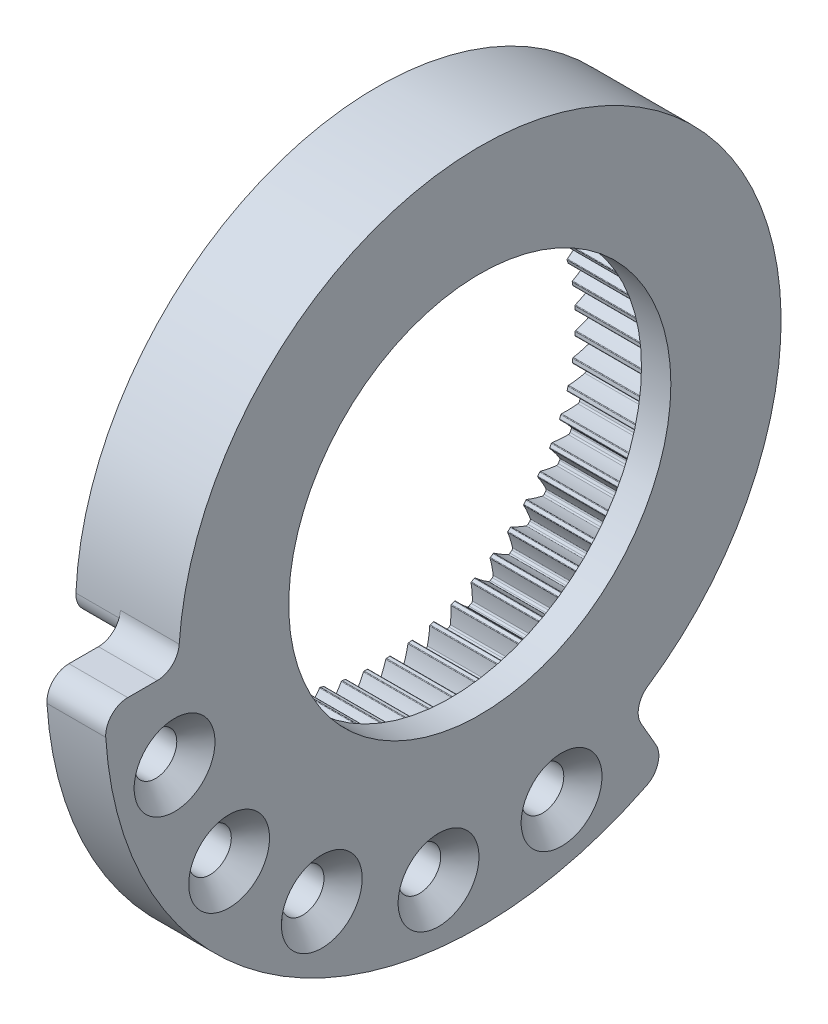
SolidWorks part; units mm, degrees
ref_plane "Plane1" through (0, 0, 0) normal (0, 0, 1) x (1, 0, 0)
ref_plane "Plane2" through (0, 0, 0) normal (0, 1, 0) x (1, 0, 0)
ref_plane "Plane3" through (0, 0, 0) normal (1, 0, 0) x (0, 0, -1)
other "Configuration Table"
sketch "HoldingSke" plane through (0, 0, 0) normal (0, 1, 0) x (1, 0, 0)
  line L0 (0, 0) -> (1.1184, -1.6581)
  line L1 (-15, 0) -> (100, 0) construction
  line L2 (0, 0) -> (-2.1039, 2.3779)
  line L3 (0, 0) -> (-11.863, 4.5341)
  line L4 (0, 0) -> (4.8292, 7.1596)
  line L5 (0, 0) -> (-23.7986, -8.8762)
  line L6 (0, 0) -> (-10.5278, -7.1032)
  line L7 (-2.1039, 2.3779) -> (3.3635, 27.1825)
  line L8 (-76.2, 2.8779) -> (-54.61, 2.8779)
  line L9 (-71.009, 38.7566) -> (-53.1078, 45.2721)
  line L10 (-76.2, 71.12) -> (104.1128, 71.12)
  line L11 (0, 0) -> (-7, 0)
  line L12 (-76.2, 101.6) -> (-76.181, 101.6)
  line L13 (24.9733, 27.94) -> (52.9518, 28.4284)
  line L14 (24.9733, 27.94) -> (24.9743, 27.94)
  line L15 (24.9733, 27.94) -> (100.4006, 29.5858)
  circle A0 centre (0, 0) radius 21
  circle A1 centre (0, 0) radius 12.7
  circle A2 centre (0, 0) radius 12.7
  dimension "Num_teeth" = 56
  dimension "Pitch_radius" = 180.3128
  dimension "Width" = 7
  dimension "Diameter" = 42
sketch "BasProSke" plane through (0, 0, 0) normal (0, 1, 0) x (1, 0, 0)
  line L0 (-10, 0) -> (60, 0) construction
  line L1 (0, 13.5) -> (0, 21)
  line L2 (0, 13.5) -> (7, 13.5)
  line L3 (7, 13.5) -> (7, 21)
  line L4 (7, 21) -> (0, 21)
  dimension "Thickness" = 7
  dimension "Diameter" = 42
revolve "Base-Revolve" add sketch "BasProSke" angle 360 about L0
sketch "TooCutSke" plane through (0, 0, 0) normal (1, 0, 0) x (0, 0, -1)
  line L3 (0.4401, 13.9931) -> (0.4401, 53.6633) construction
  line L4 (0, 0) -> (0, 59.563) construction
  line L5 (0, 0) -> (-3.8312, 68.22) construction
  line L6 (-6.1069, 11.5158) -> (37.1194, 13.9434) construction
  circle A0 centre (0, 0) radius 14 construction
  circle A1 centre (0, 0) radius 14.626 construction
  circle A2 centre (0, 0) radius 11.8401 construction
  circle A3 centre (0, 0) radius 13.4746 construction
  arc A4 (0.6176, 13.4604) -> (0.1647, 14.6251) centre (-6.1069, 11.5158) ccw
  arc A5 (0.6176, 13.4604) -> (-0.6176, 13.4604) centre (0, 0) ccw
  arc A6 (0.1647, 14.6251) -> (-0.1647, 14.6251) centre (0, 0) ccw
  arc A7 (-0.1647, 14.6251) -> (-0.6176, 13.4604) centre (6.1069, 11.5158) ccw
extrude "ToothCut" cut sketch "TooCutSke" along normal through all
fillet "Breaks" radius 0.05 2 edges at (3.5, 13.4862, 0.6101) (3.5, 13.4862, -0.6101)
fillet "RootFillets" radius 0.126 2 edges at (3.5, 14.6251, 0.1647) (3.5, 14.6251, -0.1647)
pattern_circular "TeethCuts" count 56 every 6.429 about axis through (-10, 0, 0) along (1, 0, 0) of "RootFillets", "Breaks", "ToothCut"
sketch "Sketch1" plane through (0, 0, 0) normal (-1, 0, 0) x (0, 0, 1)
  circle A0 centre (0, 0) radius 20.5
  circle A1 centre (0, 0) radius 21
  dimension "1" = 41
extrude "Cut-Extrude1" cut sketch "Sketch1" against normal through all
sketch "Sketch2" plane through (7, 0, 0) normal (1, 0, 0) x (0, 0, -1)
  circle A0 centre (0, 0) radius 20.5
  circle A1 centre (0, 0) radius 13
  dimension "7.5" = 26
extrude "Boss-Extrude1" add sketch "Sketch2" against normal blind 2
sketch "Sketch3" plane through (0, 0, 0) normal (-1, 0, 0) x (0, 0, 1)
  line L0 (0, 0) -> (28.6774, 0) construction
  line L1 (0, 0) -> (28.8819, -7.7389) construction
  line L2 (20.5, 0) -> (25.5, 0)
  line L3 (-10.2547, -17.7508) -> (-12.7547, -22.0809)
  arc A0 (-10.2547, -17.7508) -> (20.5, 0) centre (0, 0) ccw
  arc A1 (25.5, 0) -> (-12.7547, -22.0809) centre (0, 0) cw
  circle A2 centre (0, 0) radius 20.5 construction
  arc A3 (-10.2547, -17.7508) -> (20.5, 0) centre (0, 0) ccw
  dimension "D3" = 25.5
  dimension "D4" = 0
  dimension "D1" = 15
  dimension "D2" = 120
  dimension "D5" = 5
  dimension "D6" = 5
  dimension "D7" = 44.17
extrude "Boss-Extrude2" add sketch "Sketch3" against normal up to surface (7 mm away) contours A1 L2 A0 L3 up to face at (7, 0, 20.5)
sketch "Sketch4" plane through (0, 0, 0) normal (-1, 0, 0) x (0, 0, 1)
  line L0 (0, 0) -> (29.2843, 0) construction
  line L1 (20.5, 0) -> (25.5, 0) construction
  line L2 (0, 0) -> (20.7674, -5.5646) construction
  circle A0 centre (20.7674, -5.5646) radius 0.5
  arc A5 (20.5, 0) -> (-10.2547, -17.7508) centre (0, 0) ccw construction
  circle A6 centre (17.0571, -13.0884) radius 0.5
  circle A7 centre (10.75, -18.6195) radius 0.5
  circle A8 centre (2.8063, -21.3161) radius 0.5
  circle A9 centre (-5.5646, -20.7674) radius 0.5
  point P18 (0, 0)
  point P22 (0, 0)
  dimension "D2" = 1
  dimension "D1" = 15
  dimension "D3" = 21.5
  dimension "D4" = 5
extrude "Cut-Extrude2" cut sketch "Sketch4" against normal through all
sketch "Sketch5" plane through (0, 0, 0) normal (-1, 0, 0) x (0, 0, 1)
  line L0 (-10.2547, -17.7508) -> (-7.6912, -16.2708)
  line L1 (20.5, 0) -> (17.9366, -1.48)
  line L2 (20.5, 0) -> (25.5, 0) construction
  line L3 (-10.2547, -17.7508) -> (-12.7547, -22.0809) construction
  line L4 (-10.2547, -17.7508) -> (-12.7547, -22.0809)
  line L5 (20.5, 0) -> (25.5, 0)
  arc A0 (-7.6912, -16.2708) -> (17.9366, -1.48) centre (-0.0021, 0.0042) ccw
  arc A1 (25.5, 0) -> (-12.7547, -22.0809) centre (0, 0) cw
  dimension "D5" = 18
  dimension "D6" = 25.5
  dimension "D1" = 150
  dimension "D2" = 150
  dimension "D3" = 2.96
  dimension "D4" = 2.96
extrude "Cut-Extrude3" cut sketch "Sketch5" against normal blind 3
fillet "Fillet1" radius 1.5 6 edges at (5, 0, 25.5) (5, 0, 20.5) (1.5, -1.48, 17.9366) (1.5, -16.2708, -7.6912) (5, -22.0809, -12.7547) (5, -17.7508, -10.2547)
fillet "Fillet2" radius 1.5 2 edges at (1.5, -17.7508, -10.2547) (1.5, 0, 20.5)
hole_wizard "CSK for M2.5 Flat Head Machine Screw2" positions "3DSketch2" profile "Sketch7" countersink size "M2.5" standard "ANSI Metric" end condition through all
sketch3d "3DSketch2"
  line L0 (7, -20.7674, -5.5646) -> (3, -20.7674, -5.5646) construction
  line L1 (7, -21.3161, 2.8063) -> (3, -21.3161, 2.8063) construction
  line L2 (7, -18.6195, 10.75) -> (3, -18.6195, 10.75) construction
  line L3 (7, -13.0884, 17.0571) -> (3, -13.0884, 17.0571) construction
  line L4 (7, -5.5646, 20.7674) -> (3, -5.5646, 20.7674) construction
  point P0 (7, -20.7674, -5.5646)
  point P4 (7, -21.3161, 2.8063)
  point P8 (7, -18.6195, 10.75)
  point P12 (7, -13.0884, 17.0571)
  point P16 (7, -5.5646, 20.7674)
sketch "Sketch7" plane through (7, -20.7674, -5.5646) normal (0, 1, 0) x (0, 0, -1)
  line L0 (0, 0) -> (0, 7)
  line L1 (0, 7) -> (1.45, 7)
  line L2 (1.45, 7) -> (1.45, 1.3)
  line L3 (1.45, 1.3) -> (2.75, 0)
  line L5 (2.75, 0) -> (0, 0)
  line L6 (-1.45, 1.3) -> (-2.75, 0) construction
  line L11 (0, -6.35) -> (0, 107.95) construction
  dimension "Thru Hole Dia." = 2.9
  dimension "Thru Hole Depth" = 7
  dimension "Near C'Sink Dia." = 5.5
  dimension "Near C'Sink Angle" = 90
equation "' \"Module@HoldingSke\" = 6.35"
equation "' \"Num_teeth@HoldingSke\" = 24"
equation "' \"Ap@HoldingSke\" =  14.5"
equation "' \"Ap@HoldingSke\" = 14.5"
equation "' \"Width@HoldingSke\" = 12"
equation "' \"Diameter@HoldingSke\" = 8 * 25.4"
equation "' \"Show_teeth@HoldingSke\" = 100"
equation "' \"Backlash@HoldingSke\" = 0.009 * 25.4"
equation "' \"Addendum_fac@HoldingSke\" = 1.0"
equation "' \"Dedendum_fac@HoldingSke\" = 1.25"
equation "' \"Dedendum_add@HoldingSke\" = 0.00005 * 25.4"
equation "' \"Clearance_fac@HoldingSke\" = 0.25"
equation "\"Pitch@HoldingSke\" = 1 / \"Module@HoldingSke\" "
equation "\"Overcut_dia@TooCutSke\" = (\"Num_teeth@HoldingSke\" - 2 * \"Addendum_fac@HoldingSke\") / \"Pitch@HoldingSke\" - 0.002 * 25.4"
equation "\"Pitch_dia@TooCutSke\" = \"Num_teeth@HoldingSke\" / \"Pitch@HoldingSke\""
equation "\"Base_dia@TooCutSke\" = \"Num_teeth@HoldingSke\" / \"Pitch@HoldingSke\" * cos((\"Ap@HoldingSke\"  * 3.14159265 / 180)) * 0.90"
equation "\"Root_dia@TooCutSke\" = \"Num_teeth@HoldingSke\"  / \"Pitch@HoldingSke\" + 2 *  \"Dedendum_fac@HoldingSke\"/ \"Pitch@HoldingSke\" + \"Dedendum_add@HoldingSke\" * 2"
equation "\"Half_ang@TooCutSke\" = 180 / \"Num_teeth@HoldingSke\""
equation "\"Half_CT@TooCutSke\" = \"Num_teeth@HoldingSke\" / \"Pitch@HoldingSke\" * sin((3.14159265 / 2 / \"Num_teeth@HoldingSke\")) / 2 + 10 * \"Backlash@HoldingSke\" / 4"
equation "\"Flank_rad@TooCutSke\" = \"Num_teeth@HoldingSke\" / \"Pitch@HoldingSke\" / 4"
equation "\"Radius@RootFillets\"= \"Clearance_fac@HoldingSke\" / \"Pitch@HoldingSke\" + \"Dedendum_add@HoldingSke\""
equation "\"Break_rad@Breaks\" = 0.02 / \"Pitch@HoldingSke\" * 5"
equation "\"Num_teeth@TeethCuts\" = int( \"Show_teeth@HoldingSke\" ) + 1"
equation "\"Num_teeth@TeethCuts\" = ((sgn( \"Num_teeth@TeethCuts\" - \"Num_teeth@HoldingSke\" )-1)*( \"Num_teeth@TeethCuts\" - \"Num_teeth@HoldingSke\" ))/-2+ \"Num_teeth@HoldingSke\""
equation "\"Num_teeth@TeethCuts\" = ((sgn( \"Num_teeth@TeethCuts\" - 2.0)+1)*( \"Num_teeth@TeethCuts\" - 2.0))/2 +2.0"
equation "\"Angle@TeethCuts\" = 360.0 / \"Num_teeth@HoldingSke\""
equation "\"Diameter@BasProSke\" = \"Num_teeth@HoldingSke\"  / \"Pitch@HoldingSke\" + 2 *  \"Dedendum_fac@HoldingSke\"/ \"Pitch@HoldingSke\" + \"Dedendum_add@HoldingSke\" * 2 + 0.002 * 25.4"
equation "\"Diameter@BasProSke\" = ((sgn( \"Diameter@BasProSke\"  - \"Diameter@HoldingSke\" )+1)*( \"Diameter@BasProSke\"  - \"Diameter@HoldingSke\" ))/2 + \"Diameter@HoldingSke\""
equation "\"Inside_diameter@BasProSke\" =  (\"Num_teeth@HoldingSke\" - 2 * \"Addendum_fac@HoldingSke\") / \"Pitch@HoldingSke\" "
equation "\"Thickness@BasProSke\"  = \"Width@HoldingSke\""
